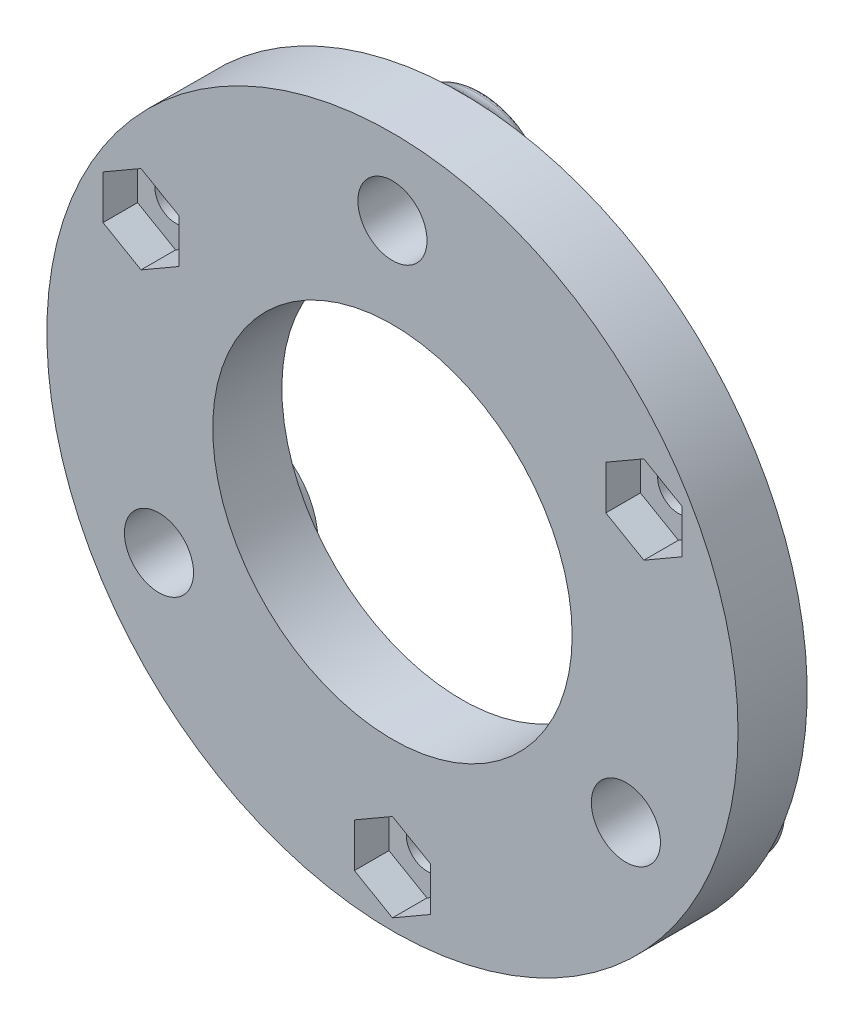
SolidWorks part; units mm, degrees
material "ABS"
ref_plane "Front Plane" through (0, 0, 0) normal (0, 0, 1) x (1, 0, 0)
ref_plane "Top Plane" through (0, 0, 0) normal (0, 1, 0) x (1, 0, 0)
ref_plane "Right Plane" through (0, 0, 0) normal (1, 0, 0) x (0, 0, -1)
sketch "Sketch2" plane through (0, 0, 0) normal (0, 0, 1) x (1, 0, 0)
  line L0 (0, 19.5) -> (0, 0) construction
  line L1 (0, 0) -> (18.1865, 10.5) construction
  circle A0 centre (0, 0) radius 25
  circle A1 centre (0, 0) radius 13
  circle A2 centre (0, 0) radius 19.5 construction
  circle A3 centre (0, 19.5) radius 2.5
  circle A4 centre (0, 0) radius 21 construction
  circle A5 centre (16.8875, -9.75) radius 2.5
  circle A8 centre (18.1865, 10.5) radius 1.5
  circle A9 centre (0, -21) radius 1.5
  circle A11 centre (0, 0) radius 8.25 construction
  circle A14 centre (0, 19.5) radius 5 construction
  circle A15 centre (0, 0) radius 14.5 construction
  circle A16 centre (-16.8875, -9.75) radius 2.5
  circle A19 centre (-18.1865, 10.5) radius 1.5
  point P17 (0, 0)
  point P24 (0, 0)
  dimension "D1" = 50
  dimension "D2" = 39
  dimension "D4" = 5
  dimension "D7" = 3
  dimension "D3" = 16.5
  dimension "D10" = 10
  dimension "D5" = 4
  dimension "D9" = 1.5
  dimension "D11" = 60
  dimension "D6" = 3
  dimension "D8" = 3
extrude "Boss-Extrude1" add sketch "Sketch2" along normal blind 5
sketch "Sketch3" plane through (0, 0, 5) normal (0, 0, 1) x (1, 0, 0)
  line L0 (0, 19.5) -> (0, 0) construction
  line L13 (-0.5774, 19.5) -> (-0.2887, 19)
  line L14 (-0.2887, 19) -> (0.2887, 19)
  line L15 (0.2887, 19) -> (0.5774, 19.5)
  line L16 (0.5774, 19.5) -> (0.2887, 20)
  line L17 (0.2887, 20) -> (-0.2887, 20)
  line L18 (-0.2887, 20) -> (-0.5774, 19.5)
  line L20 (18.1865, 7.3246) -> (20.9365, 8.9123)
  line L21 (20.9365, 8.9123) -> (20.9365, 12.0877)
  line L22 (20.9365, 12.0877) -> (18.1865, 13.6754)
  line L23 (18.1865, 13.6754) -> (15.4365, 12.0877)
  line L24 (15.4365, 12.0877) -> (15.4365, 8.9123)
  line L25 (15.4365, 8.9123) -> (18.1865, 7.3246)
  circle A0 centre (0, 19.5) radius 0.5 construction
  circle A1 centre (18.1865, 10.5) radius 2.75 construction
  dimension "D1" = 1
  dimension "D2" = 5.5
extrude "Cut-Extrude1" cut sketch "Sketch3" against normal blind 2.5
pattern_circular "CirPattern1" count 3 over 360 about axis through (0, 0, 5) along (0, 0, -1) of "Cut-Extrude1" reverse direction yes
sketch "Sketch4" plane through (0, 0, 0) normal (0, 0, -1) x (-1, 0, 0)
  circle A0 centre (0, 19.5) radius 4
  circle A1 centre (0, 19.5) radius 5
  dimension "D1" = 8
extrude "Boss-Extrude2" add sketch "Sketch4" along normal blind 1.5
fillet "Fillet1" radius 1.5 1 edges at (5, 19.5, 0)
fillet "Fillet2" radius 0.5 2 edges at (0, 24.5, -1.5) (0, 14.5, -1.5)
chamfer "Chamfer1" distance 0.25 angle 45 1 edges at (-4, 19.5, -1.5)
pattern_circular "CirPattern2" count 3 over 360 about axis through (0, 0, 5) along (0, 0, -1) of "Fillet1", "Boss-Extrude2", "Chamfer1" reverse direction yes
equation "\"Nr\" = 123"
equation "\"module\" = 0.5"
equation "\"pressure_angle\" = 20.0"
equation "\"h_a\" = 0.5"
equation "\"h_f\" = 0.625"
equation "\"clr_tip_root\" = 0.125"
equation "\"dp_r\" = 61.5"
equation "\"db_r\" = 57.79109617833337"
equation "\"fw_r\" = 8.0"
equation "\"alpha_r\" = 0.8539582918412414"
equation "\"beta_r\" = 3.171331217828824"
equation "\"bearing_ID\" = 50"
equation "\"bearing_OD\" = 65"
equation "\"bearing_height\" = 7"
equation "\"clearance_planet\" = 1.5"
equation "\"case_dist\" = 6.0"
equation "\"Motor_case_OD_max\" = 96.5"
equation "\"case_mounting_PCD\" = 89.0"
equation "\"bearing mount thickness\" = 8"
equation "\"case_mounting_hole_dia\" = 3"
equation "\"output_mounting_PCD\" = 73"
equation "\"output_mounting_hole_dia\" = 4"
equation "\"clearance_case_mount_holes_shell_thickness\" = 1"
equation "\"motor_case_OD_base\" = 87.0"
equation "\"sec_carrier_thickness\" = 5"
equation "\"sun_coupler_hub_thickness\" = 4"
equation "\"clearance_sun_coupler_sec_carrier\" = 1.5"
equation "\"clearance_motor_and_case\" = 5"
equation "\"motor_OD\" = 72"
equation "\"Motor_case_thickness\" = 2.5"
equation "\"Motor_case_ID\" = 82"
equation "\"case_mounting_hole_shift\" = 1.0"
equation "\"output_mounting_nut_wrench_size\" = 7"
equation "\"output_mounting_nut_thickness\" = 3.2"
equation "\"case_mounting_hole_allen_socket_dia\" = 5.5"
equation "\"output_mounting_nut_depth\" = 3"
equation "\"case_mounting_bolt_depth\" = 4.5"
equation "\"Ns\" = 33"
equation "\"Np\" = 45"
equation "\"ring_radial_thickness\" = 5"
equation "\"ring_OD\" = 71.5"
equation "\"ring_to_chamfer_clearance\" = 2"
equation "\"Motor_case_OD_base_to_chamfer\" = 5"
equation "\"pattern_offset_from_motor_case_OD_base\" = 3"
equation "\"pattern_bulge_dia\" = 3"
equation "\"pattern_num_bulge\" = 18"
equation "\"pattern_depth\" = 2"
equation "\"motor_height\" = 27"
equation "\"case_mounting_wrench_size\" = 5.5"
equation "\"case_mounting_nut_clearance\" = 2"
equation "\"base_plate_thickness\" = 4"
equation "\"case_mounting_nut_thickness\" = 2.4"
equation "\"case_mounting_surface_height\" = 4"
equation "\"motor_mount_hole_PCD\" = 32"
equation "\"motor_mount_hole_dia\" = 4"
equation "\"motor_mount_hole_num\" = 4"
equation "\"central_hole_offset_from_motor_mount_PCD\" = 5"
equation "\"wire_slot_dist_from_center\" = 30"
equation "\"wire_slot_length\" = 10"
equation "\"wire_slot_radius\" = 2.5"
equation "\"driver_upper_holes_dist_from_center\" = 23"
equation "\"driver_lower_holes_dist_from_center\" = 15"
equation "\"driver_side_holes_dist_from_center\" = 20"
equation "\"driver_mount_holes_dia\" = 2.5"
equation "\"driver_mount_inserts_OD\" = 3.5"
equation "\"driver_mount_thickness\" = 1.5"
equation "\"driver_mount_height\" = 4"
equation "\"air_flow_hole_offset\" = 3"
equation "\"num_planet\" = 3"
equation "\"planet_pin_bolt_dia\" = 5"
equation "\"planet_pin_socket_head_dia\" = 8.5"
equation "\"carrier_PCD\" = 39.0"
equation "\"D1@Sketch2\"=\"bearing_ID\""
equation "\"D2@Sketch2\"=\"carrier_PCD\""
equation "\"D4@Sketch2\"=\"planet_pin_bolt_dia\""
equation "\"D6@Sketch2\"=\"num_planet\""
equation "\"D8@Sketch2\"=\"num_planet\""
equation "\"D1@CirPattern1\"=\"num_planet\""
equation "\"planet_shaft_dia\" = 8"
equation "\"fw_p\" = 8.0"
equation "\"planet_shaft_step_offset\" = 1"
equation "\"carrier_trapezoidal_support_sun_offset\" = 5"
equation "\"carrier_trapezoidal_support_hole_PCD_offset_bearing_ID\" = 4"
equation "\"carrier_trapezoidal_support_hole_dia\" = 3"
equation "\"carrier_trapezoidal_support_hole_socket_head_dia\" = 5.5"
equation "\"carrier_bearing_step_width\" = 1.5"
equation "\"standard_clearance_1_5mm\" = 1.5"
equation "\"standard_fillet_1_5mm\" = 1.5"
equation "\"sun_shaft_bearing_OD\" = 16"
equation "\"sun_shaft_bearing_width\" = 5"
equation "\"standard_bearing_insertion_chamfer\" = 0.5"
equation "\"D7@Sketch2\"=\"carrier_trapezoidal_support_hole_dia\""
equation "\"D5@Sketch2\"=\"carrier_trapezoidal_support_hole_PCD_offset_bearing_ID\""
equation "\"D3@Sketch2\"=\"Ns\"*\"module\""
equation "\"carrier_trapezoidal_support_hole_wrench_size\" = 5.5"
equation "\"planet_pin_bolt_wrench_size\" = 8"
equation "\"D1@Boss-Extrude1\"=\"sec_carrier_thickness\""
equation "\"D1@Cut-Extrude1\"=\"sec_carrier_thickness\"/2"
equation "\"D1@Sketch4\"=\"planet_shaft_dia\""
equation "\"D2@Sketch4\"=\"planet_shaft_step_offset\""
equation "\"D1@Boss-Extrude2\"=\"clearance_planet\""
equation "\"D1@Fillet1\"=\"standard_fillet_1_5mm\""
equation "\"D1@Chamfer1\"=\"standard_bearing_insertion_chamfer\"/2"
equation "\"D1@Fillet2\"=\"standard_fillet_1_5mm\"/3"
equation "\"D1@CirPattern2\"=\"num_planet\""
equation "\"D10@Sketch2\"=\"planet_shaft_dia\"+\"planet_shaft_step_offset\"*2"
equation "\"D9@Sketch2\"=\"standard_clearance_1_5mm\""
equation "\"D1@Sketch3\"=\"planet_shaft_step_offset\""
equation "\"D11@Sketch2\"=180/\"num_planet\""
equation "\"D2@Sketch3\"=\"carrier_trapezoidal_support_hole_wrench_size\""
equation "\"pressure angle\" = 20.0"
equation "\"motor_output_hole_PCD\" = 22"
equation "\"motor_output_hole_dia\" = 3"
equation "\"motor_output_hole_num\" = 4"
equation "\"h_b\" = 0.625"
equation "\"dp_s\" = 16.5"
equation "\"db_s\" = 15.50492824296749"
equation "\"fw_s_calc\" = 5.95406185839039"
equation "\"alpha_s\" = 0.8539582918412449"
equation "\"beta_s\" = 3.7466288708629643"
equation "\"dp_p\" = 22.5"
equation "\"db_p\" = 21.14308396768294"
equation "\"alpha_p\" = 0.8539582918412307"
equation "\"beta_p\" = 2.2920834163175385"
equation "\"planet_bearing_OD\" = 12"
equation "\"planet_bearing_width\" = 3.5"
equation "\"planet_bore\" = 10"
equation "\"sun_shaft_bearing_ID\" = 8"
equation "\"sun_hub_dia\" = 31.0"
equation "\"sun_central_bolt_dia\" = 5"
equation "\"sun_central_bolt_socket_head_dia\" = 8.5"
equation "\"fw_s_used\" = 16.0"
equation "\"motor_output_hole_CSK_OD\" = 6"
equation "\"motor_output_hole_CSK_head_height\" = 1.5"
equation "\"bearing_retainer_thickness\" = 2"
equation "\"D4@Sketch4\"=\"carrier_trapezoidal_support_sun_offset\""
equation "\"D2@Sketch5\"=\"carrier_trapezoidal_support_hole_dia\""
equation "\"D1@Cut-Extrude2\"=\"carrier_trapezoidal_support_hole_dia\""
equation "\"D1@Sketch6\"=\"carrier_trapezoidal_support_hole_socket_head_dia\""
equation "\"D1@Cut-Extrude3\"=\"planet_pin_bolt_dia\""
equation "\"D1@Sketch7\"=\"planet_pin_socket_head_dia\""
equation "\"D1@Sketch9\"=\"sun_shaft_bearing_OD\""
equation "\"D1@Sketch10\"=\"standard_clearance_1_5mm\""
